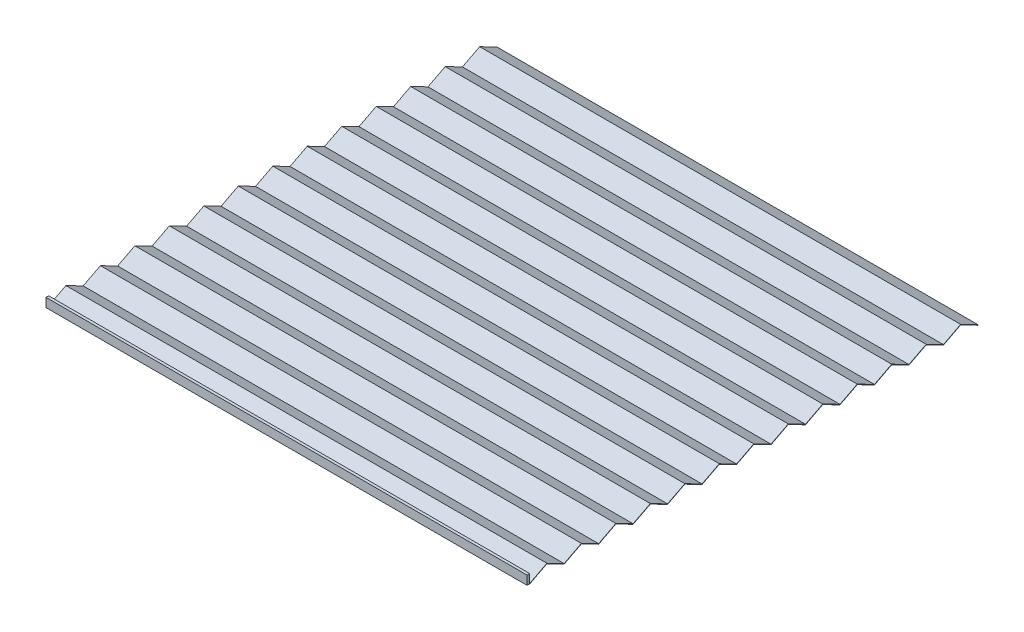
SolidWorks part; units mm, degrees
ref_plane "Front Plane" through (0, 0, 0) normal (0, 0, 1) x (1, 0, 0)
ref_plane "Top Plane" through (0, 0, 0) normal (0, 1, 0) x (1, 0, 0)
ref_plane "Right Plane" through (0, 0, 0) normal (1, 0, 0) x (0, 0, -1)
sketch "Sketch2" plane through (0, 0, 0) normal (0, 0, 1) x (1, 0, 0)
  line L1 (-270, 10) -> (270, 10)
  line L2 (-270, 10) -> (-270, 0)
  line L3 (-270, 0) -> (270, 0)
  line L4 (270, 10) -> (270, 0)
  point P4 (0, 0)
  dimension "D1" = 10
  dimension "D2" = 540
extrude "Boss-Extrude1" add sketch "Sketch2" along normal blind 3
sketch "Sketch3" plane through (270, 0, 0) normal (1, 0, 0) x (0, 0, -1)
  line L0 (0, 10) -> (503.2361, 10) construction
  line L1 (0, 0) -> (503.2361, 0) construction
  line L2 (503.2361, 10) -> (503.2361, 0) construction
  line L3 (0, 0) -> (19.3552, 10)
  line L4 (19.3552, 10) -> (38.7105, 0)
  line L5 (38.7105, 0) -> (58.0657, 10)
  line L6 (58.0657, 10) -> (77.4209, 0)
  line L7 (77.4209, 0) -> (96.7762, 10)
  line L8 (96.7762, 10) -> (116.1314, 0)
  line L9 (116.1314, 0) -> (135.4866, 10)
  line L10 (135.4866, 10) -> (154.8419, 0)
  line L11 (154.8419, 0) -> (174.1971, 10)
  line L12 (174.1971, 10) -> (193.5524, 0)
  line L13 (193.5524, 0) -> (212.9076, 10)
  line L14 (212.9076, 10) -> (232.2628, 0)
  line L15 (232.2628, 0) -> (251.6181, 10)
  line L16 (251.6181, 10) -> (270.9733, 0)
  line L17 (270.9733, 0) -> (290.3285, 10)
  line L18 (290.3285, 10) -> (309.6838, 0)
  line L20 (309.6838, 0) -> (329.039, 10)
  line L21 (329.039, 10) -> (348.3942, 0)
  line L22 (348.3942, 0) -> (367.7495, 10)
  line L23 (367.7495, 10) -> (387.1047, 0)
  line L24 (387.1047, 0) -> (406.4599, 10)
  line L25 (406.4599, 10) -> (425.8152, 0)
  line L26 (425.8152, 0) -> (445.1704, 10)
  line L27 (445.1704, 10) -> (464.5256, 0)
  line L28 (464.5256, 0) -> (483.8809, 10)
  line L29 (483.8809, 10) -> (503.2361, 0)
  line L30 (503.2361, 10) -> (503.2361, 0) construction
extrude "Extrude-Thin1" add sketch "Sketch3" against normal through all thin thin type mid plane wall 0.5
